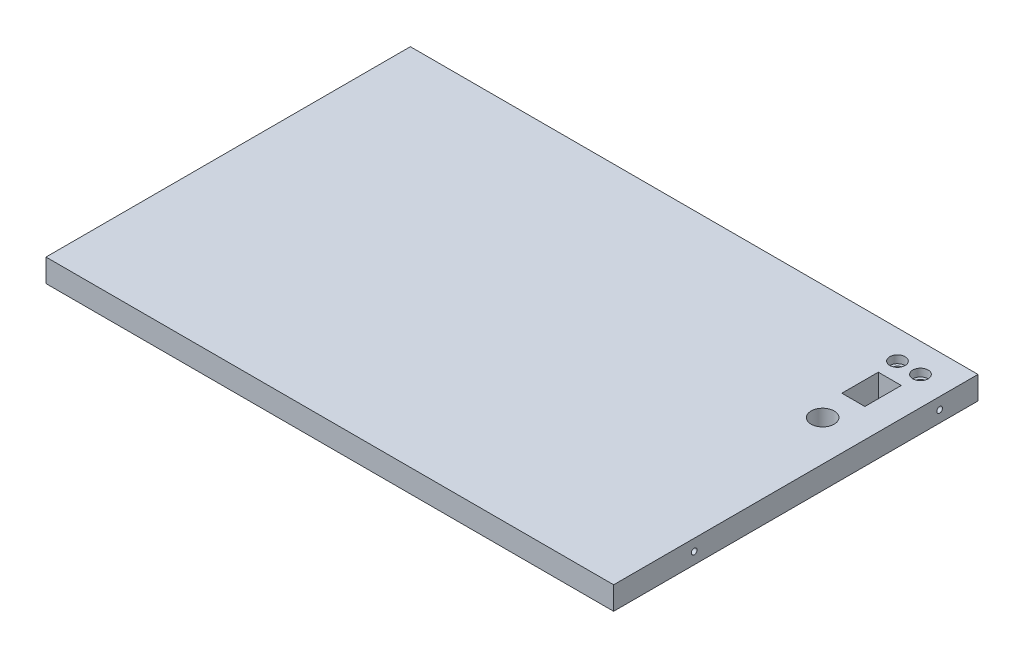
SolidWorks part; units mm, degrees
ref_plane "Front Plane" through (0, 0, 0) normal (0, 0, 1) x (1, 0, 0)
ref_plane "Top Plane" through (0, 0, 0) normal (0, 1, 0) x (1, 0, 0)
ref_plane "Right Plane" through (0, 0, 0) normal (1, 0, 0) x (0, 0, -1)
sketch "Sketch1" plane through (0, 0, 0) normal (0, 1, 0) x (1, 0, 0)
  line L0 (83.787, 122.9435) -> (83.787, -96.4922) construction
  line L1 (-191.213, 118.3124) -> (104.787, 118.3124)
  line L2 (-191.213, 118.3124) -> (-191.213, -71.6876)
  line L3 (-191.213, -71.6876) -> (104.787, -71.6876)
  line L4 (104.787, 118.3124) -> (104.787, -71.6876)
  line L5 (77.787, 93.3124) -> (89.787, 93.3124)
  line L6 (77.787, 93.3124) -> (77.787, 74.3124)
  line L7 (77.787, 74.3124) -> (89.787, 74.3124)
  line L8 (89.787, 93.3124) -> (89.787, 74.3124)
  line L9 (113.9958, 103.3124) -> (-54.987, 103.3124) construction
  circle A0 centre (83.787, 58.3124) radius 6
  circle A1 centre (89.787, 103.3124) radius 2.5
  circle A2 centre (77.787, 103.3124) radius 2.5
  point P16 (89.787, 103.3124)
  point P17 (77.787, 103.3124)
  dimension "D3" = 5
  dimension "D4" = 5
  dimension "D5" = 12
  dimension "D1" = 296
  dimension "D2" = 190
  dimension "D6" = 12
  dimension "D7" = 19
  dimension "D8" = 15
  dimension "D9" = 25
  dimension "D10" = 21
  dimension "D11" = 60
  dimension "D14" = 15
extrude "Boss-Extrude1" add sketch "Sketch1" along normal blind 12
sketch "Sketch3" plane through (0, 0, 0) normal (1, 0, 0) x (0, 0, -1)
  line L0 (-71.6876, 6) -> (118.3124, 6) construction
  line L1 (-71.6876, 12) -> (-71.6876, 0) construction
  line L2 (118.3124, 12) -> (118.3124, 0) construction
  circle A0 centre (98.3124, 6) radius 1.5
  circle A1 centre (-29.6876, 6) radius 1.5
  dimension "D2" = 3
  dimension "D3" = 3
  dimension "D1" = 20
  dimension "D4" = 148
extrude "Cut-Extrude2" cut sketch "Sketch3" against normal blind 20 from surface starting at face at (104.787, 6, -23.3124)
extrude "Cut-Extrude3" cut sketch "Sketch3<2>" along normal blind 20 from surface starting at face at (-191.213, 6, -23.3124)
sketch "Sketch3<2>" plane through (0, 0, 0) normal (1, 0, 0) x (0, 0, -1) same geometry as "Sketch3"
sketch "Sketch4" plane through (0, 0, 0) normal (0, 1, 0) x (1, 0, 0)
  circle A0 centre (89.787, 103.3124) radius 4
  circle A1 centre (77.787, 103.3124) radius 4
  dimension "D1" = 8
  dimension "D2" = 8
extrude "Cut-Extrude4" cut sketch "Sketch4" against normal blind 4 from surface starting at face at (89.787, 12, -100.8124)
